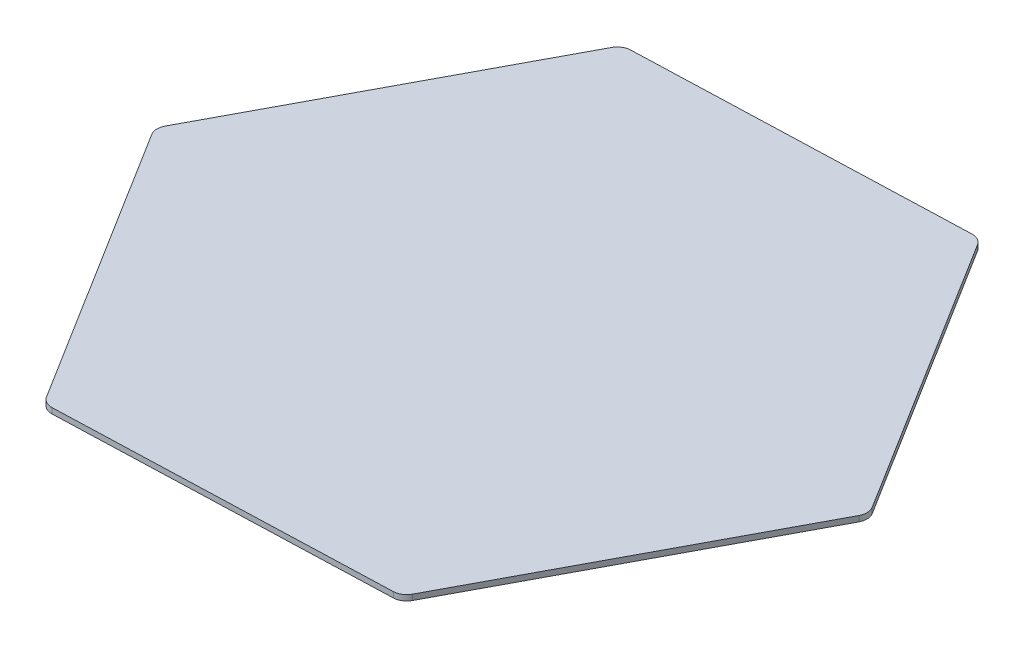
SolidWorks part; units mm, degrees
material "Thornel Mat VMA"
ref_plane "Front Plane" through (0, 0, 0) normal (0, 0, 1) x (1, 0, 0)
ref_plane "Top Plane" through (0, 0, 0) normal (0, 1, 0) x (1, 0, 0)
ref_plane "Right Plane" through (0, 0, 0) normal (1, 0, 0) x (0, 0, -1)
sketch "Sketch1" plane through (0, 0, 0) normal (0, 1, 0) x (1, 0, 0)
  line L1 (66.0232, 2.267) -> (190.6574, 6.5464)
  line L2 (190.6574, 6.5464) -> (249.2684, 116.6225)
  line L3 (249.2684, 116.6225) -> (183.2452, 222.4192)
  line L4 (183.2452, 222.4192) -> (58.611, 218.1397)
  line L5 (58.611, 218.1397) -> (0, 108.0636)
  line L6 (0, 108.0636) -> (66.0232, 2.267)
  circle A0 centre (124.6342, 112.3431) radius 108 construction
  dimension "D1" = 216
extrude "Boss-Extrude1" add sketch "Sketch1" along normal blind 2
fillet "Fillet1" radius 5 6 edges at (0, 1, -108.0636) (58.611, 1, -218.1397) (183.2452, 1, -222.4192) (249.2684, 1, -116.6225) (66.0232, 1, -2.267) (190.6574, 1, -6.5464)
